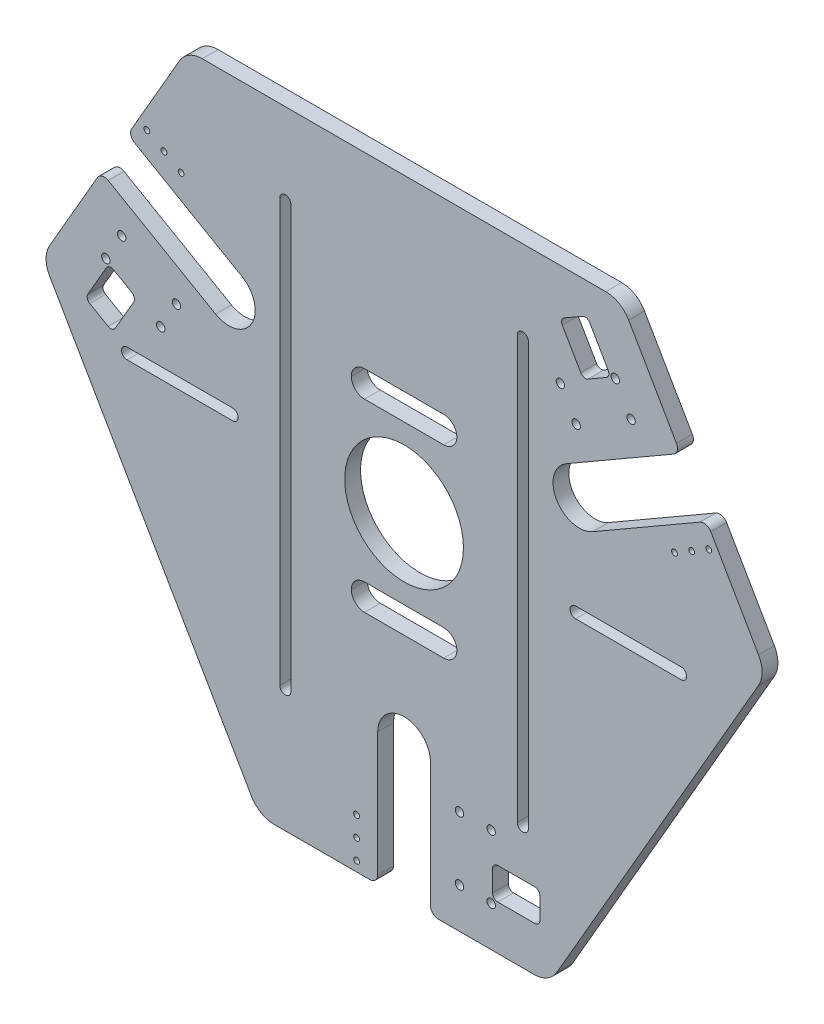
SolidWorks part; units mm, degrees
ref_plane "Front Plane" through (0, 0, 0) normal (0, 0, 1) x (1, 0, 0)
ref_plane "Top Plane" through (0, 0, 0) normal (0, 1, 0) x (1, 0, 0)
ref_plane "Right Plane" through (0, 0, 0) normal (1, 0, 0) x (0, 0, -1)
sketch "Sketch1" plane through (0, 0, 0) normal (0, 0, 1) x (1, 0, 0)
  line L0 (-100, 57.735) -> (0, 0) construction
  line L1 (0, 230.9401) -> (-200, -115.4701) construction
  line L2 (-200, -115.4701) -> (200, -115.4701) construction
  line L3 (200, -115.4701) -> (0, 230.9401) construction
  line L4 (0, 0) -> (100, 57.735) construction
  line L5 (100, 57.735) -> (0, 0) construction
  line L6 (0, 0) -> (0, -115.4701) construction
  line L7 (0, 0) -> (-109.7427, 63.36)
  line L8 (0, 0) -> (0, -126.72)
  line L9 (0, 0) -> (100, 57.735)
  line L10 (0, 0) -> (109.7427, 63.36)
  line L11 (-137.2427, 15.7286) -> (-82.2427, 110.9914)
  line L12 (-55, -126.72) -> (55, -126.72)
  line L13 (82.2427, 110.9914) -> (137.2427, 15.7286)
  line L14 (-82.2427, 110.9914) -> (82.2427, 110.9914)
  line L15 (137.2427, 15.7286) -> (55, -126.72)
  line L16 (-55, -126.72) -> (-137.2427, 15.7286)
  circle A0 centre (0, 0) radius 115.4701 construction
  point P15 (-109.7427, 63.36)
  point P18 (0, -126.72)
  point P21 (109.7427, 63.36)
  dimension "D1" = 400
  dimension "D2" = 110
extrude "Boss-Extrude1" add sketch "Sketch1" along normal blind 6 contours L16 L12 L8 L7 L11 | L14 L11 L7 L9 L10 L13 | L15 L13 L10 L9 L8 L12 region at (-58.1278, -33.5601, 0) region at (58.1278, -33.5601, 0) region at (0, 67.1202, 0)
sketch "Sketch3" plane through (0, 0, 6) normal (0, 0, 1) x (1, 0, 0)
  line L0 (-114.7427, 54.6997) -> (-104.7427, 72.0203)
  line L1 (-137.2427, 15.7286) -> (-82.2427, 110.9914) construction
  line L2 (-57.7812, 33.36) -> (-52.7812, 42.0203)
  line L3 (-52.7812, 42.0203) -> (-62.7812, 24.6997)
  line L4 (-62.7812, 24.6997) -> (-114.7427, 54.6997)
  line L5 (-52.7812, 42.0203) -> (-104.7427, 72.0203)
  line L6 (52.7812, 42.0203) -> (104.7427, 72.0203)
  line L7 (62.7812, 24.6997) -> (114.7427, 54.6997)
  line L8 (104.7427, 72.0203) -> (114.7427, 54.6997)
  line L9 (57.7812, 33.36) -> (62.7812, 24.6997)
  line L10 (62.7812, 24.6997) -> (52.7812, 42.0203)
  line L11 (10, -66.72) -> (10, -126.72)
  line L12 (-10, -66.72) -> (-10, -126.72)
  line L13 (10, -126.72) -> (-10, -126.72)
  line L14 (0, -66.72) -> (-10, -66.72)
  line L15 (-10, -66.72) -> (10, -66.72)
  line L16 (-109.7427, 63.36) -> (-57.7812, 33.36) construction
  line M6 (137.2427, 15.7286) -> (82.2427, 110.9914)
  line M8 (-82.2427, 110.9914) -> (-137.2427, 15.7286)
  line M10 (-55, -126.72) -> (55, -126.72)
  dimension "D1" = 3
  dimension "D2" = 60
  dimension "D3" = 55
  dimension "D4" = 20
extrude "Cut-Extrude2" cut sketch "Sketch3" against normal blind 6 contours L16 L0 L4 L3 | L16 L2 L5 M8 | L10 L9 L7 L6 M6 | L15 L14 L12 L11 M10 region at (-86.262, 44.0299, 6) region at (-81.262, 52.6901, 6) region at (83.762, 48.36, 6) region at (0, -96.72, 6)
sketch "Sketch4" plane through (0, 0, 6) normal (0, 0, 1) x (1, 0, 0)
  line L13 (-111.8569, 25.8981) -> (-101.4646, 19.8981)
  line L14 (-101.4646, 19.8981) -> (-110.4646, 4.3097)
  line L15 (-110.4646, 4.3097) -> (-120.8569, 10.3097)
  line L16 (-120.8569, 10.3097) -> (-111.8569, 25.8981)
  line L17 (69.3569, 99.5103) -> (58.9646, 93.5103)
  line L18 (78.3569, 83.9219) -> (67.9646, 77.9219)
  line L21 (78.3569, 83.9219) -> (69.3569, 99.5103)
  line L23 (58.9646, 93.5103) -> (67.9646, 77.9219)
  line L25 (33.5, -97.82) -> (51.5, -97.82)
  line L26 (51.5, -97.82) -> (51.5, -109.82)
  line L27 (51.5, -109.82) -> (33.5, -109.82)
  line L28 (33.5, -109.82) -> (33.5, -97.82)
  circle A0 centre (21, -87.47) radius 1.6
  circle A1 centre (33, -87.47) radius 1.6
  circle A2 centre (21, -111.47) radius 1.6
  circle A3 centre (33, -111.47) radius 1.6
  circle A4 centre (-86.2512, 25.5485) radius 1.6
  circle A5 centre (-92.2512, 15.1562) radius 1.6
  circle A6 centre (-113.0359, 27.1562) radius 1.6
  circle A7 centre (-107.0359, 37.5485) radius 1.6
  circle A8 centre (65.2512, 61.9215) radius 1.6
  circle A9 centre (59.2512, 72.3138) radius 1.6
  circle A10 centre (80.0359, 84.3138) radius 1.6
  circle A11 centre (86.0359, 73.9215) radius 1.6
  dimension "D1" = 3
  dimension "D4" = 3.2
  dimension "D5" = 3.2
  dimension "D6" = 3.2
  dimension "D7" = 3.2
  dimension "D2" = 18
  dimension "D3" = 18
extrude "Cut-Extrude3" cut sketch "Sketch4" against normal blind 10
fillet "Fillet1" radius 2 4 edges at (33.5, -109.82, 3) (33.5, -97.82, 3) (51.5, -109.82, 3) (51.5, -97.82, 3)
fillet "Fillet2" radius 2 4 edges at (-120.8569, 10.3097, 3) (-110.4646, 4.3097, 3) (-111.8569, 25.8981, 3) (-101.4646, 19.8981, 3)
sketch "Sketch5" plane through (0, 0, 6) normal (0, 0, 1) x (1, 0, 0)
  circle A0 centre (115.4951, 45.8965) radius 1.1
  circle A1 centre (109, 42.1465) radius 1.1
  circle A2 centre (102.5048, 38.3965) radius 1.1
  circle A3 centre (-18, -122.97) radius 1.1
  circle A4 centre (-18, -115.47) radius 1.1
  circle A5 centre (-18, -107.97) radius 1.1
  circle A6 centre (-97.4951, 77.0735) radius 1.1
  circle A7 centre (-91, 73.3235) radius 1.1
  circle A8 centre (-84.5048, 69.5735) radius 1.1
  dimension "D1" = 3
extrude "Cut-Extrude4" cut sketch "Sketch5" against normal blind 10
sketch "Sketch6" plane through (0, 0, 6) normal (0, 0, 1) x (1, 0, 0)
  circle A0 centre (0, 0) radius 22.5
  point P0 (0, 0)
  dimension "D1" = 45
extrude "Cut-Extrude5" cut sketch "Sketch6" against normal blind 10
sketch "Sketch7" plane through (0, 0, 6) normal (0, 0, 1) x (1, 0, 0)
  line L2 (-42.9, 0) -> (-45, 0)
  line L4 (0, 110.9914) -> (0, 0)
  line L5 (-82.2427, 110.9914) -> (82.2427, 110.9914) construction
  line L6 (-47.1, 80) -> (-47.1, -80)
  line L7 (-42.9, -80) -> (-42.9, 80)
  line L8 (42.9, 80) -> (42.9, -80)
  line L9 (47.1, -80) -> (47.1, 80)
  line L10 (-105, 2.1) -> (-65, 2.1)
  line L11 (-105, -2.1) -> (-65, -2.1)
  line L12 (65, 2.1) -> (105, 2.1)
  line L13 (65, -2.1) -> (105, -2.1)
  arc A8 (42.9, -80) -> (47.1, -80) centre (45, -80) ccw
  arc A9 (-47.1, -80) -> (-42.9, -80) centre (-45, -80) ccw
  arc A16 (47.1, 80) -> (42.9, 80) centre (45, 80) ccw
  arc A17 (-42.9, 80) -> (-47.1, 80) centre (-45, 80) ccw
  arc A34 (-65, -2.1) -> (-65, 2.1) centre (-65, 0) ccw
  arc A36 (-105, 2.1) -> (-105, -2.1) centre (-105, 0) ccw
  arc A37 (65, 2.1) -> (65, -2.1) centre (65, 0) ccw
  arc A39 (105, -2.1) -> (105, 2.1) centre (105, 0) ccw
  dimension "D7" = 0
  dimension "D6" = 0
fillet "Fillet4" 2 edges at (-10, -66.72, 3) (10, -66.72, 3) type full round first side face at (-10, -96.72, 3) second side face at (10, -96.72, 3) middle face at (0, -66.72, 3)
fillet "Fillet5" 2 edges at (52.7812, 42.0203, 3) (62.7812, 24.6997, 3) type full round first side face at (78.762, 57.0203, 3) second side face at (88.762, 39.6997, 3) middle face at (57.7812, 33.36, 3)
fillet "Fillet6" 2 edges at (-62.7812, 24.6997, 3) (-52.7812, 42.0203, 3) type full round first side face at (-88.762, 39.6997, 3) second side face at (-78.762, 57.0203, 3) middle face at (-57.7812, 33.36, 3)
fillet "Fillet7" radius 10 6 edges at (-137.2427, 15.7286, 3) (-55, -126.72, 3) (55, -126.72, 3) (137.2427, 15.7286, 3) (82.2427, 110.9914, 3) (-82.2427, 110.9914, 3)
fillet "Fillet8" radius 3 6 edges at (-10, -126.72, 3) (10, -126.72, 3) (-114.7427, 54.6997, 3) (-104.7427, 72.0203, 3) (114.7427, 54.6997, 3) (104.7427, 72.0203, 3)
sketch "Sketch8" plane through (0, 0, 6) normal (0, 0, 1) x (1, 0, 0)
  line L1 (-20, 40) -> (20, 40)
  line L2 (-20, 40) -> (-20, 30)
  line L3 (-20, 30) -> (20, 30)
  line L4 (20, 40) -> (20, 30)
  line L5 (-20, 40) -> (20, 30) construction
  line L6 (-20, 30) -> (20, 40) construction
  line L7 (-20, -30) -> (20, -30)
  line L8 (-20, -30) -> (-20, -40)
  line L9 (-20, -40) -> (20, -40)
  line L10 (20, -30) -> (20, -40)
  line L11 (-20, -30) -> (20, -40) construction
  line L12 (-20, -40) -> (20, -30) construction
  point P0 (0, 35)
  point P5 (0, -35)
  dimension "D1" = 40
  dimension "D2" = 10
  dimension "D3" = 40
  dimension "D4" = 10
  dimension "D5" = 30
  dimension "D6" = 20
  dimension "D7" = 30
  dimension "D8" = 0
extrude "Cut-Extrude11" cut sketch "Sketch8" against normal blind 10
fillet "Fillet9" radius 5 8 edges at (20, -40, 3) (20, -30, 3) (-20, -40, 3) (-20, -30, 3) (20, 30, 3) (20, 40, 3) (-20, 30, 3) (-20, 40, 3)
extrude "Cut-Extrude13" cut sketch "Sketch7" against normal blind 10 contours L13 A39 L12 A37 | L9 A16 L8 A8 | L7 A17 L6 A9 | L10 A36 L11 A34 region at (-45, 80.4575, 6) region at (45, 0, 6) region at (-85, 0, 6) region at (85, 0, 6)
fillet "Fillet10" radius 2 4 edges at (67.9646, 77.9219, 3) (58.9646, 93.5103, 3) (69.3569, 99.5103, 3) (78.3569, 83.9219, 3)
